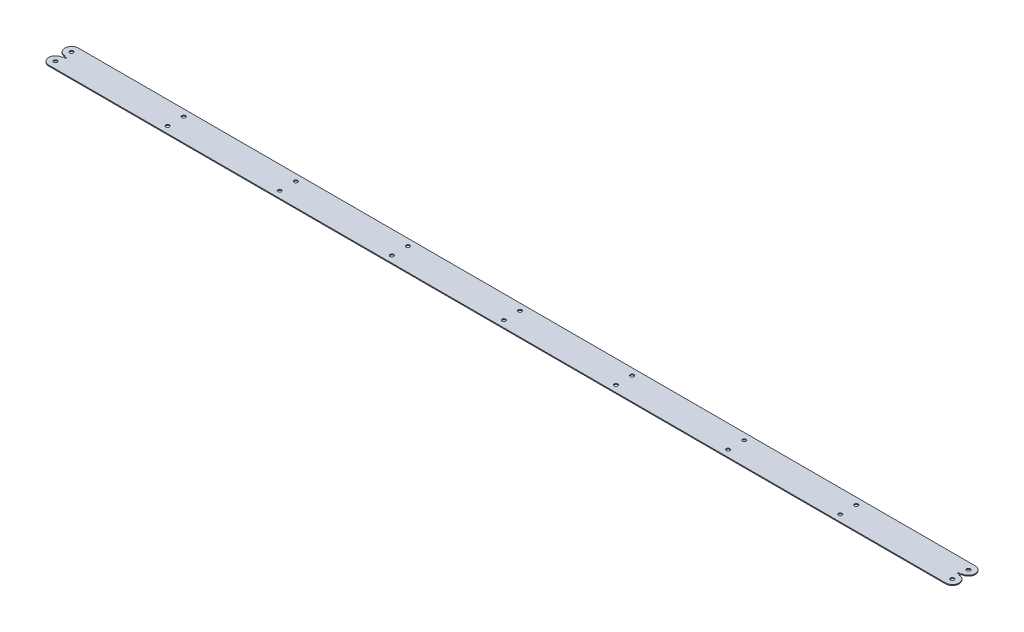
SolidWorks part; units mm, degrees
ref_plane "Front Plane" through (0, 0, 0) normal (0, 0, 1) x (1, 0, 0)
ref_plane "Top Plane" through (0, 0, 0) normal (0, 1, 0) x (1, 0, 0)
ref_plane "Right Plane" through (0, 0, 0) normal (1, 0, 0) x (0, 0, -1)
sketch "Sketch1" plane through (0, 0, 0) normal (0, 1, 0) x (1, 0, 0)
  line L0 (-500, 0) -> (500, 0) construction
  line L5 (-500, 7.5) -> (500, 7.5) construction
  line L6 (-500, 7.5) -> (-500, -7.5) construction
  line L19 (-500, -7.5) -> (500, -7.5)
  line L25 (500, 7.5) -> (500, -7.5) construction
  line L53 (-500, 7.5) -> (500, -7.5) construction
  line L95 (-500, -7.5) -> (500, 7.5) construction
  line L197 (-507.433, -1) -> (-507.5, -1)
  line L198 (-507.5, -1) -> (-507.5, 1)
  line L200 (-507.5, 1) -> (-507.433, 1)
  line L201 (-500, 7.5) -> (-500, 10.5) construction
  line L202 (0, 0) -> (0, 18) construction
  line L203 (500, 7.5) -> (500, 10.5) construction
  line L204 (500, 25.5) -> (-500, 25.5)
  line L205 (500, 25.5) -> (500, 10.5) construction
  line L206 (500, 10.5) -> (-500, 10.5) construction
  line L207 (-500, 25.5) -> (-500, 10.5) construction
  line L208 (500, 25.5) -> (-500, 10.5) construction
  line L209 (500, 10.5) -> (-500, 25.5) construction
  line L210 (-497, 8.5) -> (-497, 9.5)
  line L211 (500, 18) -> (-500, 18) construction
  line L212 (-500, 7.5) -> (-500, 8.5)
  line L213 (-500, 8.5) -> (-497, 8.5)
  line L214 (-497, 9.5) -> (-500, 9.5)
  line L215 (-500, 9.5) -> (-500, 10.5)
  line L216 (500, 10.5) -> (500, 9.5)
  line L217 (500, 9.5) -> (497, 9.5)
  line L218 (497, 9.5) -> (497, 8.5)
  line L219 (497, 8.5) -> (500, 8.5)
  line L220 (500, 8.5) -> (500, 7.5)
  line L221 (500, 9) -> (497, 9) construction
  line L222 (497, 9) -> (-497, 9) construction
  line L223 (-497, 9) -> (-500, 9) construction
  circle A70 centre (0, 0) radius 2
  arc A71 (-500, 7.5) -> (-500, -7.5) centre (-500, 0) ccw construction
  arc A72 (500, -7.5) -> (500, 7.5) centre (500, 0) ccw construction
  circle A73 centre (125, 0) radius 2
  circle A74 centre (250, 0) radius 2
  circle A75 centre (375, 0) radius 2
  circle A76 centre (500, 0) radius 2
  circle A77 centre (-125, 0) radius 2
  circle A78 centre (-250, 0) radius 2
  circle A79 centre (-375, 0) radius 2
  circle A80 centre (-500, 0) radius 2
  arc A81 (-500, 25.5) -> (-500, 10.5) centre (-500, 18) ccw
  arc A82 (500, 10.5) -> (500, 25.5) centre (500, 18) ccw
  arc A83 (500, -7.5) -> (500, 7.5) centre (500, 0) ccw
  arc A84 (-500, -7.5) -> (-507.433, -1) centre (-500, 0) cw
  arc A85 (-507.433, 1) -> (-500, 7.5) centre (-500, 0) cw
  circle A86 centre (0, 18) radius 2
  circle A87 centre (125, 18) radius 2
  circle A88 centre (250, 18) radius 2
  circle A89 centre (375, 18) radius 2
  circle A90 centre (500, 18) radius 2
  circle A91 centre (-125, 18) radius 2
  circle A92 centre (-250, 18) radius 2
  circle A93 centre (-375, 18) radius 2
  circle A94 centre (-500, 18) radius 2
  point P29 (-507.5, 0)
  dimension "D1" = 1000
  dimension "D3" = 4
  dimension "D7" = 5
  dimension "D9" = 1
  dimension "D2" = 5
  dimension "D5" = 2
  dimension "D6" = 15
  dimension "D10" = 3
  dimension "D13" = 125
  dimension "D14" = 125
  dimension "D15" = 33
  dimension "D8" = 5
  dimension "D11" = 3
  dimension "D12" = 125
extrude "Boss-Extrude1" add sketch "Sketch1" along normal blind 1
